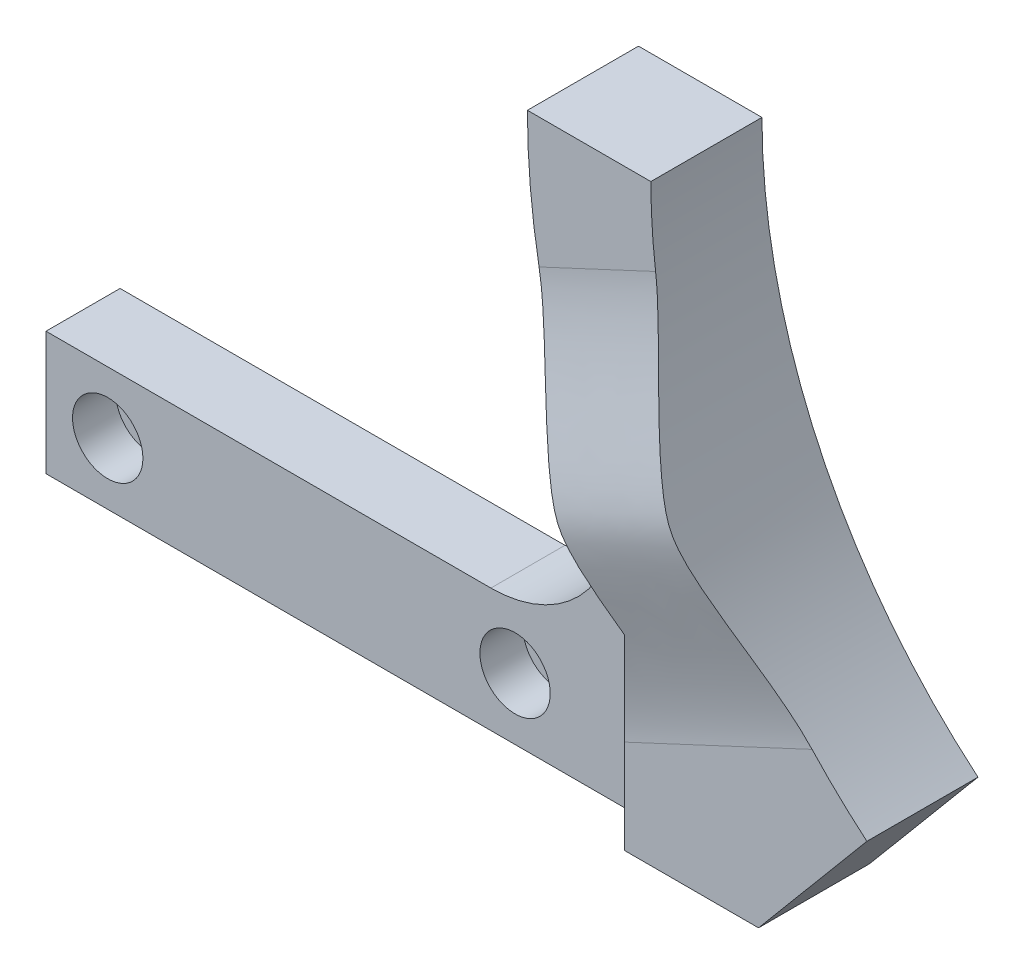
SolidWorks part; units mm, degrees
ref_plane "Front Plane" through (0, 0, 0) normal (1, 0, 0) x (0, 1, 0)
ref_plane "Top Plane" through (0, 0, 0) normal (0, 0, 1) x (0, 1, 0)
ref_plane "Right Plane" through (0, 0, 0) normal (0, 1, 0) x (-1, 0, 0)
sketch "Sketch1" plane through (0, 0, 0) normal (0, 0, 1) x (0, 1, 0)
  line L0 (0, 0) -> (-37.5362, 31.4966) construction
  line L1 (0, 0) -> (0, 49) construction
  line L2 (-37.5362, 31.4966) -> (-40.2173, 33.7463)
  line L3 (0, 49) -> (0, 52.5)
  line L4 (0, 0) -> (-22.1875, 47.5812) construction
  line L5 (0, 52.5) -> (0, 59)
  line L6 (-48, 101) -> (-38, 101)
  line L7 (-48, 101) -> (-48, 45.1331)
  line L8 (-48, 45.1331) -> (-38, 45.1331)
  line L9 (-38, 101) -> (-38, 45.1331)
  line L10 (-40.2173, 33.7463) -> (-48, 40.2768)
  line L11 (-48, 40.2768) -> (-48, 45.1331)
  circle A0 centre (-43, 63) radius 1.6
  circle A1 centre (-43, 96) radius 1.6
  circle A2 centre (0, 0) radius 45 construction
  arc A3 (-37.5362, 31.4966) -> (0, 49) centre (0, 0) ccw construction
  arc A4 (0, 52.5) -> (-22.1875, 47.5812) centre (0, 0) ccw construction
  arc A5 (-40.2173, 33.7463) -> (0, 52.5) centre (0, 0) ccw construction
  arc A6 (0, 49) -> (-37.5362, 31.4966) centre (0, 0) ccw
  arc A7 (-22.1875, 47.5812) -> (-40.2173, 33.7463) centre (0, 0) ccw construction
  circle A8 centre (-43, 63) radius 2.85
  circle A9 centre (-43, 96) radius 2.85
  arc A10 (0, 59) -> (-38, 45.1331) centre (0, 0) ccw
  point P21 (-48, 40.7124)
  point P22 (-47.2488, 40.7124)
  point P23 (0, 0)
  dimension "D1" = 3.2
  dimension "D2" = 3.2
  dimension "D6" = 90
  dimension "D7" = 98
  dimension "D8" = 105
  dimension "D14" = 5.7
  dimension "D15" = 5.7
  dimension "D3" = 33
  dimension "D4" = 43
  dimension "D5" = 63
  dimension "D9" = 25
  dimension "D10" = 25
  dimension "D11" = 5
  dimension "D12" = 10
  dimension "D13" = 5
  dimension "D16" = 10
extrude "Boss-Extrude1" add sketch "Sketch1" along normal blind 12 contours L8 L11 A6 L3 region at (-47.1318, -23.9574, 0)
extrude "Boss-Extrude2" add sketch "Sketch1<3>" along normal blind 6 contours L9 L6 L7 L8 A9 A8 region at (-72.4198, -43, 0)
sketch "Sketch1<3>" plane through (0, 0, 0) normal (0, 0, 1) x (0, 1, 0) same geometry as "Sketch1"
extrude "Boss-Extrude3" add sketch "Sketch1<4>" along normal offset from surface (2.5 mm away) 3.5 contours A9 A1 | A8 A0 region at (-63, -45.7694, 0) region at (-96, -45.7694, 0) up to face at (-93.15, -43, 6)
sketch "Sketch1<4>" plane through (0, 0, 0) normal (0, 0, 1) x (0, 1, 0) same geometry as "Sketch1"
chamfer "Chamfer3" distance 15 angle 45 1 edges at (-45.1331, -38, 3) first distance on face at (-52.0232, -23.2902, 6)
chamfer "Chamfer4" distance 9 angle 45 1 edges at (-45.1331, -43, 6)
ref_plane "Plane1" through (-40.2483, -18.7681, 0) normal (0.9063, 0.4226, 0) x (0, 0, -1)
sketch "Sketch3" plane through (-40.2483, -18.7681, 0) normal (0.9063, 0.4226, 0) x (0, 0, -1)
  line L0 (-9, 34.7824) -> (-9, -42.7172) construction
  line L1 (0, -20.7083) -> (0, 20.7083) construction
  line L2 (-12, 20.7083) -> (-12, -20.7083) construction
  line L3 (-12, 2.5829) -> (-12, -4.2967) construction
  line L4 (-9, 12.8992) -> (-9, 7.1782) construction
  line L5 (-9, -12.3215) -> (-9, -19.1417) construction
  line L6 (-9, -15) -> (-9, -26.4811)
  line L7 (-12, -26.4811) -> (0, -26.4811) construction
  line L8 (-9, -26.4811) -> (-21.9403, -26.4811)
  line L9 (-21.9403, -26.4811) -> (-21.9403, 24.9345)
  line L10 (-9, 15) -> (-9, 24.9345)
  line L11 (-9, 24.9345) -> (-21.9403, 24.9345)
  line L12 (-12, 24.9345) -> (0, 24.9345) construction
  spline S0 degree 3 poles (-9, -15) (-9, -10.5) (-11.9363, -3.2355) (-12.1024, 2.675) (-9, 10.5) (-9, 15) knots 0 0 0 0 0.483457 0.583457 1 1 1 1
  point P15 (0, 0)
  point P24 (-9, -26.4811)
  dimension "D2" = 15
  dimension "D3" = 15
  dimension "D5" = 20
  dimension "D1" = 9
  dimension "D4" = 30
  dimension "D6" = 15
extrude "Cut-Extrude2" cut sketch "Sketch3" against normal blind 27.5
fillet "Fillet1" radius 10 1 edges at (-55.7787, -38, 3)
equation "\"D10@Sketch1\"=\"D9@Sketch1\""
equation "\"D3@Sketch3\"=\"D2@Sketch3\""
equation "\"D6@Sketch3\"=\"D4@Sketch3\"/2"
